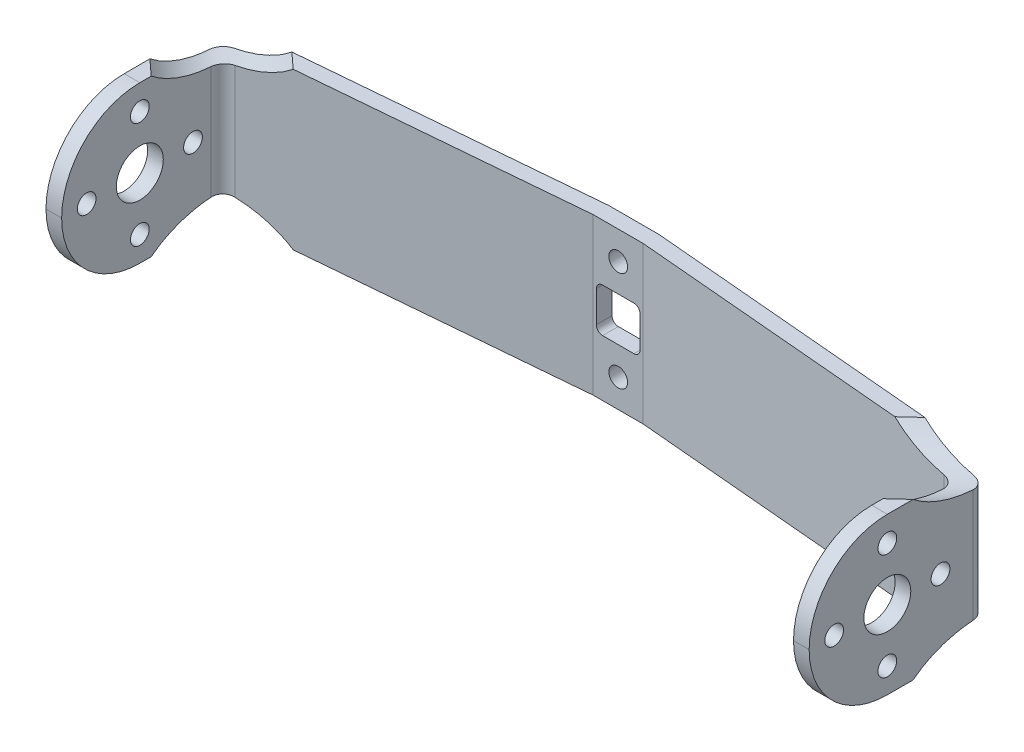
SolidWorks part; units mm, degrees
material "ABS"
ref_plane "Plano frontal" through (0, 0, 0) normal (0, 0, 1) x (1, 0, 0)
ref_plane "Plano superior" through (0, 0, 0) normal (0, 1, 0) x (1, 0, 0)
ref_plane "Plano direito" through (0, 0, 0) normal (1, 0, 0) x (0, 0, -1)
sketch "Esboço1" plane through (0, 0, 0) normal (0, 1, 0) x (1, 0, 0)
  line L0 (-83.493, -40.1032) -> (-85.993, -40.1032)
  line L1 (-85.993, -40.1032) -> (-85.993, -12.1032)
  line L2 (33.507, -14.394) -> (-20.993, -9.6259)
  line L3 (36.007, -12.1032) -> (-20.993, -7.1163)
  line L4 (-83.493, -14.394) -> (-28.993, -9.6259)
  line L5 (-85.993, -12.1032) -> (-28.993, -7.1163)
  line L6 (-83.493, -40.1032) -> (-83.493, -14.394)
  line L7 (-20.993, -7.1163) -> (-28.993, -7.1163)
  line L9 (36.007, -40.1032) -> (33.507, -40.1032)
  line L12 (33.507, -14.394) -> (33.507, -40.1032)
  line L13 (36.007, -12.1032) -> (36.007, -40.1032)
  line L16 (-28.993, -9.6259) -> (-20.993, -9.6259)
  dimension "D1" = 95
  dimension "D2" = 95
  dimension "D3" = 95
  dimension "D4" = 95
extrude "Ressalto-extrusão1" add sketch "Esboço1" along normal blind 25
fillet "Filete1" radius 12.5 4 edges at (34.757, 25, 40.1032) (34.757, 0, 40.1032) (-84.743, 0, 40.1032) (-84.743, 25, 40.1032)
fillet "Filete2" radius 2 4 edges at (-83.493, 12.5, 14.394) (-85.993, 12.5, 12.1032) (36.007, 12.5, 12.1032) (33.507, 12.5, 14.394)
ref_plane "Plano1" through (-39.8025, 0, -36.4723) normal (0.7373, 0, 0.6756) x (0.6756, 0, -0.7373)
sketch "Esboço2" plane through (0, 0, 7.1163) normal (0, 0, -1) x (-1, 0, 0)
  line L0 (28.993, 25) -> (28.993, 0) construction
  line L2 (27.493, 9) -> (22.493, 9)
  line L3 (28.493, 10) -> (28.493, 15)
  line L4 (27.493, 16) -> (22.493, 16)
  line L5 (21.493, 10) -> (21.493, 15)
  line L6 (20.993, 0) -> (28.993, 0) construction
  circle A0 centre (24.993, 4.5) radius 1.5
  circle A1 centre (24.993, 20.5) radius 1.5
  arc A2 (22.493, 9) -> (21.493, 10) centre (22.493, 10) cw
  arc A3 (22.493, 16) -> (21.493, 15) centre (22.493, 15) ccw
  arc A4 (28.493, 15) -> (27.493, 16) centre (27.493, 15) ccw
  arc A5 (27.493, 9) -> (28.493, 10) centre (27.493, 10) ccw
  point P14 (21.493, 9)
  point P19 (28.493, 16)
  point P22 (28.493, 9)
  dimension "D1" = 4
  dimension "D2" = 4
  dimension "D8" = 3
  dimension "D9" = 3
  dimension "D10" = 4.5
  dimension "D11" = 1
  dimension "D3" = 4.5
  dimension "D4" = 4.5
  dimension "D5" = 7
  dimension "D6" = 7
  dimension "D7" = 0.5
extrude "Corte-extrusão1" cut sketch "Esboço2" against normal blind 10
sketch "Esboço3" plane through (36.007, 0, 0) normal (1, 0, 0) x (0, 0, -1)
  line L2 (-27.6032, 25) -> (-13.9359, 25) construction
  circle A0 centre (-27.6032, 12.5) radius 3.75
  circle A1 centre (-36.1032, 12.5) radius 1.5
  circle A2 centre (-19.1032, 12.5) radius 1.5
  circle A3 centre (-27.6032, 4) radius 1.5
  circle A4 centre (-27.6032, 21) radius 1.5
  dimension "D1" = 3
  dimension "D2" = 3
  dimension "D3" = 3
  dimension "D4" = 3
  dimension "D5" = 17
  dimension "D7" = 7.5
  dimension "D8" = 8.5
  dimension "D9" = 8.5
  dimension "D10" = 8.5
  dimension "D11" = 8.5
  dimension "D12" = 8.5
  dimension "D13" = 12.5
  dimension "D14" = 12.5
  dimension "D15" = 12.5
extrude "Corte-extrusão2" cut sketch "Esboço3" against normal through all
sketch "Esboço4" plane through (-39.8025, 0, -36.4723) normal (0.7373, 0, 0.6756) x (0.6756, 0, -0.7373)
  line L0 (-68.3706, 12.5) -> (-68.3706, 32.5)
  line L1 (-68.3706, 25) -> (-68.3706, 0) construction
  line L2 (-68.3706, 32.5) -> (-67.3706, 32.5)
  line L3 (-68.3706, 12.5) -> (-68.3706, -7.5)
  line L4 (-68.3706, -7.5) -> (-67.3706, -7.5)
  circle A0 centre (-67.3706, 32.5) radius 11
  circle A1 centre (-67.3706, -7.5) radius 11
extrude "Corte-extrusão5" cut sketch "Esboço4" along normal blind 17 and the other way blind 17
ref_plane "Plano2" through (-24.993, 0, 0) normal (1, 0, 0) x (0, 0, -1)
mirror "Espelhar1" about plane through (-24.993, 0, 0) normal (1, 0, 0) of "Corte-extrusão5"
